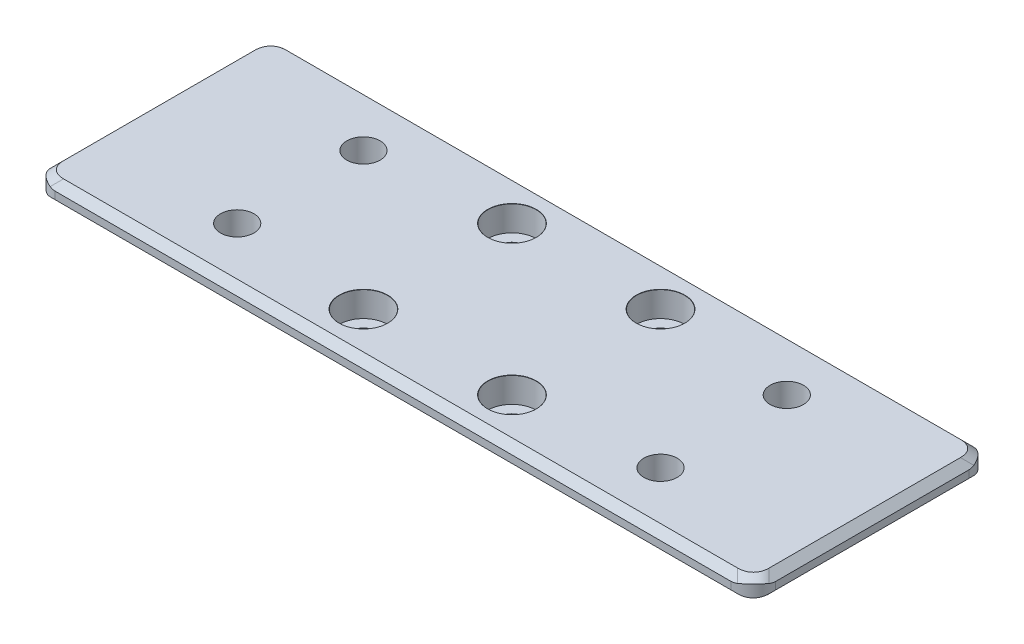
SolidWorks part; units mm, degrees
ref_plane "Front Plane" through (0, 0, 0) normal (0, 0, 1) x (1, 0, 0)
ref_plane "Top Plane" through (0, 0, 0) normal (0, 1, 0) x (1, 0, 0)
ref_plane "Right Plane" through (0, 0, 0) normal (1, 0, 0) x (0, 0, -1)
sketch "Sketch1" plane through (0, 0, 0) normal (0, 1, 0) x (1, 0, 0)
  line L1 (-48.5, 16) -> (48.5, 16)
  line L2 (-48.5, 16) -> (-48.5, -16)
  line L3 (-48.5, -16) -> (48.5, -16)
  line L4 (48.5, 16) -> (48.5, -16)
  line L5 (-48.5, 16) -> (48.5, -16) construction
  line L6 (-48.5, -16) -> (48.5, 16) construction
  point P0 (0, 0)
  dimension "D1" = 32
  dimension "D2" = 97
extrude "Boss-Extrude1" add sketch "Sketch1" along normal blind 5
sketch "Sketch2" plane through (0, 5, 0) normal (0, 1, 0) x (1, 0, 0)
  line L1 (-28.5, -8.5) -> (28.5, -8.5) construction
  line L2 (-28.5, -8.5) -> (-28.5, 8.5) construction
  line L3 (-28.5, 8.5) -> (28.5, 8.5) construction
  line L4 (28.5, -8.5) -> (28.5, 8.5) construction
  line L5 (-28.5, -8.5) -> (28.5, 8.5) construction
  line L6 (-28.5, 8.5) -> (28.5, -8.5) construction
  point P0 (0, 0)
  dimension "D1" = 17
  dimension "D2" = 57
hole_wizard "Hole1" positions "Sketch3" profile "Sketch4" legacy
sketch "Sketch3" plane through (0, 5, 0) normal (0, 1, 0) x (1, 0, 0)
  point P0 (-28.5, 8.5)
  point P3 (-28.5, -8.5)
  point P6 (28.5, -8.5)
  point P9 (28.5, 8.5)
sketch "Sketch4" plane through (-28.5, 5, -8.5) normal (1, 0, 0) x (0, 0, 1)
  line L0 (0, 0) -> (0, 6)
  line L1 (0, 6) -> (2.25, 6)
  line L2 (2.25, 6) -> (2.25, 0)
  line L3 (2.25, 0) -> (0, 0)
  line L4 (0, 110) -> (0, -10) construction
  dimension "Diameter" = 4.5
  dimension "Depth" = 6
chamfer "Chamfer1" distance 1 angle 45 4 edges at (0, 5, 16) (48.5, 5, 0) (0, 5, -16) (-48.5, 5, 0)
chamfer "Chamfer2" distance 3 angle 45 4 edges at (48.5, 0, 0) (0, 0, 16) (-48.5, 0, 0) (0, 0, -16)
fillet "Fillet1" radius 3 12 edges at (-48.5, 3.5, 16) (-48.5, 3.5, -16) (48.5, 3.5, -16) (48.5, 3.5, 16) (47, 1.5, 14.5) (47, 1.5, -14.5) (-47, 1.5, -14.5) (-47, 1.5, 14.5) (-48, 4.5, -15.5) (48, 4.5, 15.5) (-48, 4.5, 15.5) (48, 4.5, -15.5)
sketch "Sketch5" plane through (0, 5, 0) normal (0, 1, 0) x (1, 0, 0)
  line L0 (-10, 10) -> (10, 10) construction
  line L6 (10, 10) -> (10, -10) construction
  line L7 (-15, -16) -> (15, -16) construction
  line L8 (-15, -16) -> (-15, 16) construction
  line L9 (-15, 16) -> (15, 16) construction
  line L10 (15, -16) -> (15, 16) construction
  line L11 (-15, -16) -> (15, 16) construction
  line L12 (-15, 16) -> (15, -16) construction
  line L13 (10, -10) -> (-10, -10) construction
  line L14 (-10, -10) -> (-10, 10) construction
  line L15 (-45.5, 16) -> (45.5, 16) construction
  line L16 (45.5, -16) -> (-45.5, -16) construction
  circle A0 centre (-10, 10) radius 1.5 construction
  circle A1 centre (10, 10) radius 1.5 construction
  circle A2 centre (10, -10) radius 1.5 construction
  circle A3 centre (-10, -10) radius 1.5 construction
  point P0 (0, 0)
  point P8 (0, 0)
  dimension "D1" = 3
  dimension "D2" = 4.5
  dimension "D5" = 17
  dimension "D6" = 17
  dimension "D7" = 3.5
  dimension "D3" = 30
hole_wizard "CBORE for M3 Hex Socket Head Cap Screw1" positions "Sketch6" profile "Sketch7" counterbore size "M3" standard "ISO" end condition through all
sketch "Sketch6" plane through (0, 5, 0) normal (0, 1, 0) x (1, 0, 0)
  point P0 (10, 10)
  point P3 (-10, 10)
  point P6 (10, -10)
  point P9 (-10, -10)
sketch "Sketch7" plane through (10, 5, -10) normal (1, 0, 0) x (0, 0, 1)
  line L0 (0, 0) -> (0, 5)
  line L1 (0, 5) -> (1.7, 5)
  line L3 (1.7, 5) -> (1.7, 3.4)
  line L4 (3.25, 3.4) -> (1.7, 3.4)
  line L5 (3.25, 3.4) -> (3.25, 0.025)
  line L6 (3.25, 0.025) -> (3.275, 0)
  line L7 (3.275, 0) -> (0, 0)
  line L8 (-3.25, 0.025) -> (-3.275, 0) construction
  line L11 (0, -6.35) -> (0, 107.95) construction
  dimension "Thru Hole Dia." = 3.4
  dimension "Thru Hole Depth" = 5
  dimension "C'Bore Dia." = 6.5
  dimension "C'Bore Depth" = 3.4
  dimension "Near C'Sink Dia." = 6.55
  dimension "Near C'Sink Angle" = 90
